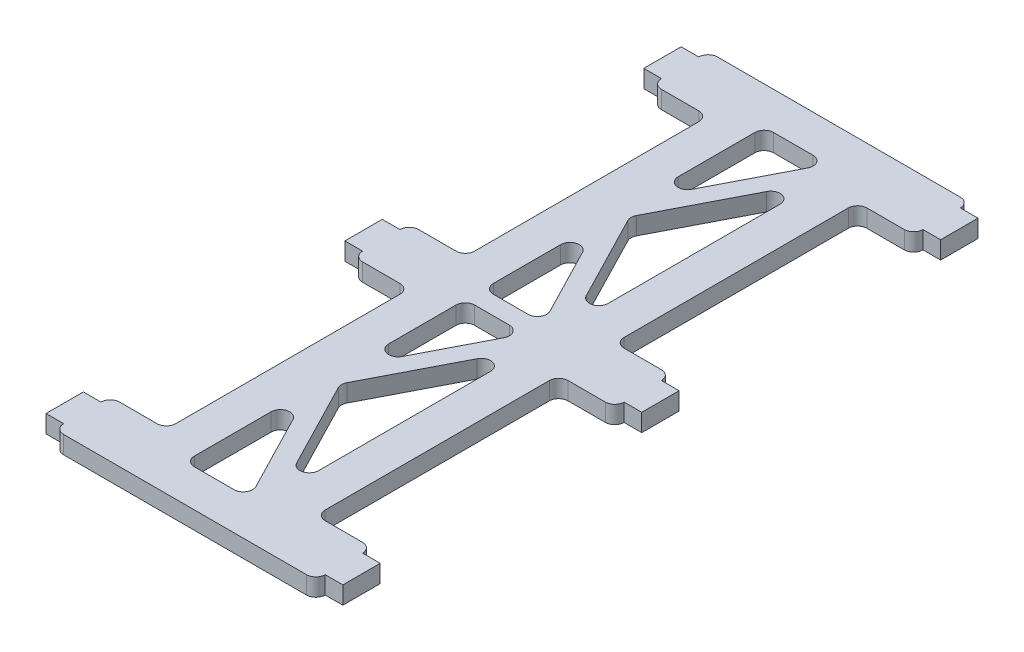
SolidWorks part; units mm, degrees
ref_plane "Front Plane" through (0, 0, 0) normal (0, 0, 1) x (1, 0, 0)
ref_plane "Top Plane" through (0, 0, 0) normal (0, 1, 0) x (1, 0, 0)
ref_plane "Right Plane" through (0, 0, 0) normal (1, 0, 0) x (0, 0, -1)
sketch "Sketch1" plane through (0, 34.29, 0) normal (0, 1, 0) x (1, 0, 0)
  line L0 (16.0528, 190.5) -> (19.05, 190.5) construction
  line L1 (0, -190.5) -> (0, 187.198) construction
  line L2 (38.1028, 187.198) -> (35.1028, 187.198) construction
  line L3 (35.1028, -190.5) -> (38.1, -190.5) construction
  line L5 (-12.7, 65.0875) -> (12.7, 65.0875)
  line L6 (-12.7, 65.0875) -> (-12.7, 176.2125)
  line L7 (-12.7, 176.2125) -> (12.7, 176.2125)
  line L8 (12.7, 65.0875) -> (12.7, 176.2125)
  line L9 (-12.7, 65.0875) -> (12.7, 176.2125) construction
  line L10 (-12.7, 176.2125) -> (12.7, 65.0875) construction
  point P0 (0, 120.65)
  dimension "D1" = 111.125
  dimension "D2" = 25.4
  dimension "D3" = 14.2875
extrude "Boss-Extrude1" add sketch "Sketch1" along normal mid plane 3 contours L7 L8 L5 L6
sketch "Sketch2" plane through (0, 35.79, 0) normal (0, 1, 0) x (1, 0, 0)
  line L0 (0, 176.2125) -> (0, 65.0186) construction
  line L1 (-12.7, 176.2125) -> (12.7, 176.2125) construction
  line L2 (12.7, 120.65) -> (-12.7, 120.65) construction
  line L3 (12.7, 65.0875) -> (12.7, 176.2125) construction
  line L4 (-12.7, 65.0875) -> (-12.7, 176.2125) construction
  line L5 (-22.225, 176.2125) -> (-12.7, 166.6875) construction
  line L6 (22.225, 166.6875) -> (12.7, 166.6875)
  line L7 (22.225, 166.6875) -> (22.225, 176.2125)
  line L8 (22.225, 176.2125) -> (12.7, 176.2125)
  line L9 (12.7, 166.6875) -> (12.7, 176.2125)
  line L10 (22.225, 166.6875) -> (12.7, 176.2125) construction
  line L11 (22.225, 176.2125) -> (12.7, 166.6875) construction
  line L12 (-22.225, 166.6875) -> (-12.7, 176.2125) construction
  line L13 (-12.7, 166.6875) -> (-12.7, 176.2125)
  line L14 (-22.225, 176.2125) -> (-12.7, 176.2125)
  line L15 (-22.225, 166.6875) -> (-22.225, 176.2125)
  line L16 (-22.225, 166.6875) -> (-12.7, 166.6875)
  line L17 (22.225, 115.8875) -> (12.7, 115.8875)
  line L18 (22.225, 115.8875) -> (22.225, 125.4125)
  line L19 (22.225, 125.4125) -> (12.7, 125.4125)
  line L20 (12.7, 115.8875) -> (12.7, 125.4125)
  line L21 (22.225, 115.8875) -> (12.7, 125.4125) construction
  line L22 (22.225, 125.4125) -> (12.7, 115.8875) construction
  line L23 (-12.7, 115.8875) -> (-12.7, 125.4125)
  line L24 (-22.225, 125.4125) -> (-12.7, 125.4125)
  line L25 (-22.225, 115.8875) -> (-22.225, 125.4125)
  line L26 (-22.225, 115.8875) -> (-12.7, 115.8875)
  line L27 (-22.225, 125.4125) -> (-12.7, 115.8875) construction
  line L28 (-22.225, 115.8875) -> (-12.7, 125.4125) construction
  line L29 (22.225, 65.0875) -> (12.7, 65.0875)
  line L30 (22.225, 65.0875) -> (22.225, 74.6125)
  line L31 (22.225, 74.6125) -> (12.7, 74.6125)
  line L32 (12.7, 65.0875) -> (12.7, 74.6125)
  line L33 (22.225, 65.0875) -> (12.7, 74.6125) construction
  line L34 (22.225, 74.6125) -> (12.7, 65.0875) construction
  line L35 (-12.7, 65.0875) -> (-12.7, 74.6125)
  line L36 (-22.225, 74.6125) -> (-12.7, 74.6125)
  line L37 (-22.225, 65.0875) -> (-22.225, 74.6125)
  line L38 (-22.225, 65.0875) -> (-12.7, 65.0875)
  line L39 (-22.225, 74.6125) -> (-12.7, 65.0875) construction
  line L40 (-22.225, 65.0875) -> (-12.7, 74.6125) construction
  point P11 (17.4625, 171.45)
  point P21 (-17.4625, 171.45)
  point P24 (17.4625, 120.65)
  point P33 (-17.4625, 120.65)
  point P34 (17.4625, 69.85)
  point P43 (-17.4625, 69.85)
  dimension "D1" = 9.525
  dimension "D2" = 9.525
  dimension "D3" = 3
extrude "Boss-Extrude2" add sketch "Sketch2" against normal up to surface (3 mm away) up to face at (0, 32.79, -120.65)
sketch "Sketch4" plane through (0, 35.79, 0) normal (0, 1, 0) x (1, 0, 0)
  line L0 (12.7, 125.4125) -> (12.7, 166.6875) construction
  line L1 (-6.35, 169.8625) -> (6.35, 169.8625)
  line L2 (-6.35, 169.8625) -> (-6.35, 71.4375)
  line L3 (-6.35, 71.4375) -> (6.35, 71.4375)
  line L4 (6.35, 169.8625) -> (6.35, 71.4375)
  line L5 (-6.35, 169.8625) -> (6.35, 71.4375) construction
  line L6 (-6.35, 71.4375) -> (6.35, 169.8625) construction
  line L7 (-12.7, 125.4125) -> (-12.7, 166.6875) construction
  line L8 (-22.225, 176.2125) -> (22.225, 176.2125) construction
  line L9 (-22.225, 65.0875) -> (22.225, 65.0875) construction
  line L10 (-6.35, 96.0438) -> (6.35, 96.0438) construction
  line L12 (-6.35, 96.0438) -> (6.35, 120.65) construction
  line L13 (6.35, 120.65) -> (-6.35, 145.2563) construction
  line L14 (6.35, 71.4375) -> (-6.35, 96.0438) construction
  line L15 (-6.35, 145.2563) -> (6.35, 145.2563) construction
  line L17 (7.7607, 72.1656) -> (-4.6953, 96.299)
  line L18 (-6.35, 145.2563) -> (6.35, 169.8625) construction
  line L19 (6.35, 120.65) -> (-6.35, 120.65) construction
  line L20 (-7.7607, 96.7718) -> (4.9393, 121.3781)
  line L21 (4.9393, 70.7094) -> (-8.0047, 95.7885)
  line L22 (6.35, 119.0625) -> (-6.35, 119.0625)
  line L23 (4.9393, 119.9219) -> (-8.1365, 145.2562)
  line L24 (-8.1365, 145.2562) -> (4.9393, 170.5906)
  line L25 (-4.6953, 96.299) -> (7.9145, 169.5933) construction
  line L26 (-4.9393, 95.3157) -> (7.7607, 119.9219)
  line L27 (-6.35, 96.0438) -> (6.35, 169.8625) construction
  line L29 (6.35, 122.2375) -> (-6.35, 122.2375)
  line L30 (-8.0047, 95.7885) -> (4.7855, 170.1317) construction
  line L31 (7.7607, 121.3781) -> (-4.5635, 145.2563)
  line L32 (-4.5635, 145.2563) -> (7.7607, 169.1344)
  point P0 (0, 120.65)
  dimension "D1" = 6.35
  dimension "D2" = 6.35
  dimension "D3" = 6.35
  dimension "D4" = 6.35
  dimension "D7" = 1.5875
  dimension "D8" = 1.5875
  dimension "D9" = 1.5875
  dimension "D10" = 1.5875
extrude "Cut-Extrude1" cut sketch "Sketch4" against normal through all contours L3 L21 L2 | L26 L17 L4 | L20 L22 L2 | L29 L23 L2 | L32 L31 L4 | L2 L24 L1 region at (-2.7122, 35.79, -162.8142) region at (-2.9853, 35.79, -128.7567) region at (2.7122, 35.79, -145.2563) region at (-2.9853, 35.79, -112.5433) region at (-2.7122, 35.79, -78.4858) region at (2.7122, 35.79, -96.0438)
fillet "Fillet1" radius 1.5875 38 edges at (-6.35, 34.29, -92.5825) (6.35, 34.29, -74.8988) (22.225, 34.29, -65.0875) (22.225, 34.29, -74.6125) (12.7, 34.29, -74.6125) (12.7, 34.29, -115.8875) (22.225, 34.29, -115.8875) (22.225, 34.29, -125.4125) (12.7, 34.29, -125.4125) (12.7, 34.29, -166.6875) (22.225, 34.29, -166.6875) (22.225, 34.29, -176.2125) (-22.225, 34.29, -166.6875) (-12.7, 34.29, -166.6875) (-12.7, 34.29, -125.4125) (-22.225, 34.29, -125.4125) (-22.225, 34.29, -115.8875) (-12.7, 34.29, -115.8875) (-12.7, 34.29, -74.6125) (-22.225, 34.29, -74.6125) (-22.225, 34.29, -65.0875) (4.5635, 34.29, -71.4375) (-22.225, 34.29, -176.2125) (-6.35, 34.29, -141.795) (3.7442, 34.29, -122.2375) (-6.35, 34.29, -122.2375) (6.35, 34.29, -117.1887) (6.35, 34.29, -124.1113) (-4.5635, 34.29, -145.2563) (6.35, 34.29, -166.4012) (-6.35, 34.29, -169.8625) (4.5635, 34.29, -169.8625) (-6.35, 34.29, -148.7175) (-6.35, 34.29, -99.505) (-6.35, 34.29, -119.0625) (3.7442, 34.29, -119.0625) (-6.35, 34.29, -71.4375) (-4.5635, 34.29, -96.0438)
sketch "Sketch5" plane through (0, 35.79, 0) normal (0, 1, 0) x (1, 0, 0)
  line L0 (22.225, 168.275) -> (22.225, 174.625) construction
  line L1 (25.225, 168.275) -> (22.225, 168.275)
  line L2 (25.225, 168.275) -> (25.225, 174.625)
  line L3 (25.225, 174.625) -> (22.225, 174.625)
  line L4 (22.225, 168.275) -> (22.225, 174.625)
  line L5 (25.225, 168.275) -> (22.225, 174.625) construction
  line L6 (25.225, 174.625) -> (22.225, 168.275) construction
  line L7 (22.225, 168.275) -> (22.225, 174.625) construction
  line L8 (22.225, 171.45) -> (23.725, 171.45) construction
  line L9 (0, 196.0278) -> (0, 0) construction
  line L10 (-22.225, 171.45) -> (-23.725, 171.45) construction
  line L11 (-25.225, 174.625) -> (-22.225, 168.275) construction
  line L12 (-25.225, 168.275) -> (-22.225, 174.625) construction
  line L13 (-22.225, 168.275) -> (-22.225, 174.625)
  line L14 (-25.225, 174.625) -> (-22.225, 174.625)
  line L15 (-25.225, 168.275) -> (-25.225, 174.625)
  line L16 (-25.225, 168.275) -> (-22.225, 168.275)
  line L17 (25.225, 117.475) -> (22.225, 117.475)
  line L18 (25.225, 117.475) -> (25.225, 123.825)
  line L19 (25.225, 123.825) -> (22.225, 123.825)
  line L20 (22.225, 117.475) -> (22.225, 123.825)
  line L21 (25.225, 117.475) -> (22.225, 123.825) construction
  line L22 (25.225, 123.825) -> (22.225, 117.475) construction
  line L23 (22.225, 120.65) -> (23.725, 120.65) construction
  line L24 (-22.225, 117.475) -> (-22.225, 123.825)
  line L25 (-25.225, 123.825) -> (-22.225, 123.825)
  line L26 (-25.225, 117.475) -> (-25.225, 123.825)
  line L27 (-25.225, 117.475) -> (-22.225, 117.475)
  line L28 (-22.225, 120.65) -> (-23.725, 120.65) construction
  line L29 (-25.225, 123.825) -> (-22.225, 117.475) construction
  line L30 (-25.225, 117.475) -> (-22.225, 123.825) construction
  line L31 (25.225, 66.675) -> (22.225, 66.675)
  line L32 (25.225, 66.675) -> (25.225, 73.025)
  line L33 (25.225, 73.025) -> (22.225, 73.025)
  line L34 (22.225, 66.675) -> (22.225, 73.025)
  line L35 (25.225, 66.675) -> (22.225, 73.025) construction
  line L36 (25.225, 73.025) -> (22.225, 66.675) construction
  line L37 (22.225, 69.85) -> (23.725, 69.85) construction
  line L38 (-22.225, 66.675) -> (-22.225, 73.025)
  line L39 (-25.225, 73.025) -> (-22.225, 73.025)
  line L40 (-25.225, 66.675) -> (-25.225, 73.025)
  line L41 (-25.225, 66.675) -> (-22.225, 66.675)
  line L42 (-22.225, 69.85) -> (-23.725, 69.85) construction
  line L43 (-25.225, 73.025) -> (-22.225, 66.675) construction
  line L44 (-25.225, 66.675) -> (-22.225, 73.025) construction
  line L45 (-23.725, 171.45) -> (-23.725, 120.65) construction
  point P0 (23.725, 171.45)
  point P7 (23.725, 120.65)
  point P21 (-23.725, 171.45)
  point P35 (-23.725, 120.65)
  point P36 (23.725, 69.85)
  point P49 (-23.725, 69.85)
  dimension "D1" = 3
  dimension "D2" = 6.35
  dimension "D4" = 50.8
  dimension "D3" = 3
extrude "Boss-Extrude3" add sketch "Sketch5" against normal up to surface (3 mm away) up to face at (-2.8486, 32.79, -113.8749)
